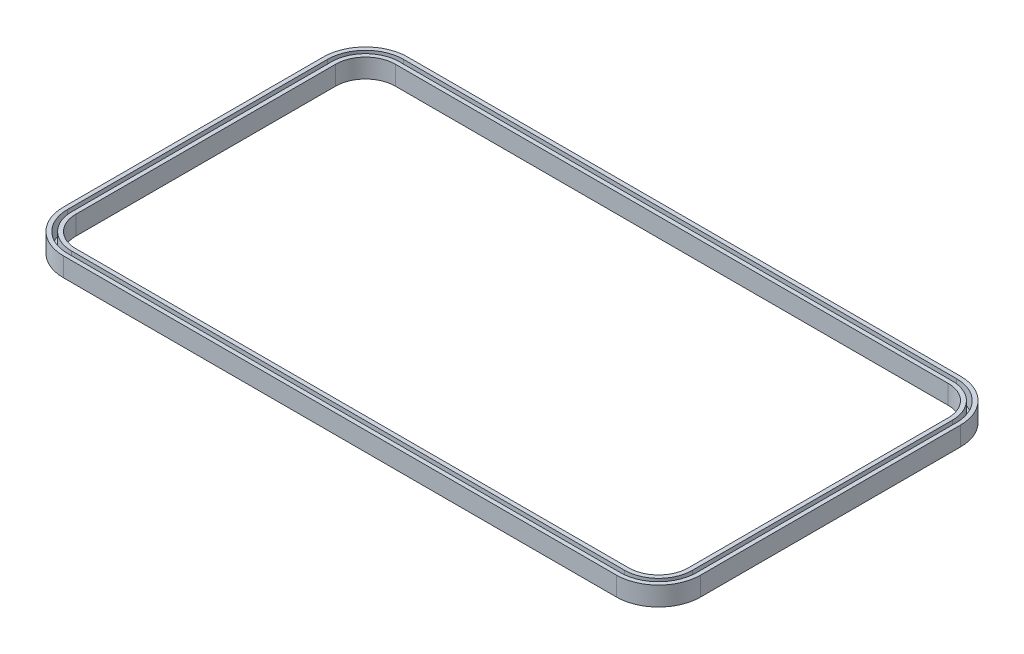
SolidWorks part; units mm, degrees
ref_plane "前视基准面" through (0, 0, 0) normal (0, 0, 1) x (1, 0, 0)
ref_plane "上视基准面" through (0, 0, 0) normal (0, 1, 0) x (1, 0, 0)
ref_plane "右视基准面" through (0, 0, 0) normal (1, 0, 0) x (0, 0, -1)
other "Configuration Table"
sketch "草图2" plane through (0, 0, 0) normal (0, 1, 0) x (1, 0, 0)
  line L1 (-167, 104) -> (167, 104)
  line L2 (-192.5, 78.5) -> (-192.5, -78.5)
  line L3 (-167, -104) -> (167, -104)
  line L4 (192.5, 78.5) -> (192.5, -78.5)
  line L5 (-192.5, 104) -> (192.5, -104) construction
  line L6 (-192.5, -104) -> (192.5, 104) construction
  arc A0 (167, 104) -> (192.5, 78.5) centre (167, 78.5) cw
  arc A1 (167, -104) -> (192.5, -78.5) centre (167, -78.5) ccw
  arc A2 (-192.5, -78.5) -> (-167, -104) centre (-167, -78.5) ccw
  arc A3 (-167, 104) -> (-192.5, 78.5) centre (-167, 78.5) ccw
  point P0 (0, 0)
  dimension "D3" = 25.5
  dimension "D1" = 385
  dimension "D2" = 208
extrude "凸台-拉伸1" add sketch "草图2" along normal blind 11.5
sketch "草图3" plane through (0, 11.5, 0) normal (0, 1, 0) x (1, 0, 0)
  line L0 (-167, -104) -> (167, -104) construction
  line L1 (-167, 96.5) -> (167, 96.5)
  line L2 (-185, 78.5) -> (-185, -78.5)
  line L3 (-167, -96.5) -> (167, -96.5)
  line L4 (185, 78.5) -> (185, -78.5)
  line L5 (-185, 96.5) -> (185, -96.5) construction
  line L6 (-185, -96.5) -> (185, 96.5) construction
  line L7 (-192.5, 78.5) -> (-192.5, -78.5) construction
  arc A0 (167, 96.5) -> (185, 78.5) centre (167, 78.5) cw
  arc A1 (167, -96.5) -> (185, -78.5) centre (167, -78.5) ccw
  arc A2 (-185, -78.5) -> (-167, -96.5) centre (-167, -78.5) ccw
  arc A3 (-167, 96.5) -> (-185, 78.5) centre (-167, 78.5) ccw
  point P0 (0, 0)
  dimension "D4" = 18
  dimension "D1" = 370
  dimension "D2" = 7.5
  dimension "D3" = 7.5
  dimension "D5" = 193
extrude "切除-拉伸1" cut sketch "草图3" against normal through all and the other way through all
sketch "草图6" plane through (0, 11.5, 0) normal (0, 1, 0) x (1, 0, 0)
  line L0 (-192.5, 78.5) -> (-192.5, -78.5) construction
  line L1 (-167, 101.5) -> (167, 101.5)
  line L2 (-190, 78.5) -> (-190, -78.5)
  line L3 (-167, -101.5) -> (167, -101.5)
  line L4 (190, 78.5) -> (190, -78.5)
  line L5 (-190, 101.5) -> (190, -101.5) construction
  line L6 (-190, -101.5) -> (190, 101.5) construction
  line L7 (167, 104) -> (-167, 104) construction
  line L8 (-185, 78.5) -> (-185, -78.5) construction
  line L9 (-167, 99) -> (167, 99)
  line L10 (-187.5, 78.5) -> (-187.5, -78.5)
  line L11 (-167, -99) -> (167, -99)
  line L12 (187.5, 78.5) -> (187.5, -78.5)
  line L13 (-187.5, 99) -> (187.5, -99) construction
  line L14 (-187.5, -99) -> (187.5, 99) construction
  line L15 (167, 96.5) -> (-167, 96.5) construction
  arc A0 (167, -101.5) -> (190, -78.5) centre (167, -78.5) ccw
  arc A1 (167, 101.5) -> (190, 78.5) centre (167, 78.5) cw
  arc A2 (-167, 101.5) -> (-190, 78.5) centre (-167, 78.5) ccw
  arc A3 (-190, -78.5) -> (-167, -101.5) centre (-167, -78.5) ccw
  arc A4 (-167, 99) -> (-187.5, 78.5) centre (-167, 78.5) ccw
  arc A5 (167, 99) -> (187.5, 78.5) centre (167, 78.5) cw
  arc A6 (167, -99) -> (187.5, -78.5) centre (167, -78.5) ccw
  arc A7 (-187.5, -78.5) -> (-167, -99) centre (-167, -78.5) ccw
  point P0 (0, 0)
  point P22 (0, 0)
  dimension "D3" = 23
  dimension "D6" = 20.5
  dimension "D1" = 2.5
  dimension "D2" = 2.5
  dimension "D4" = 2.5
  dimension "D5" = 2.5
extrude "切除-拉伸3" cut sketch "草图6" against normal blind 10
